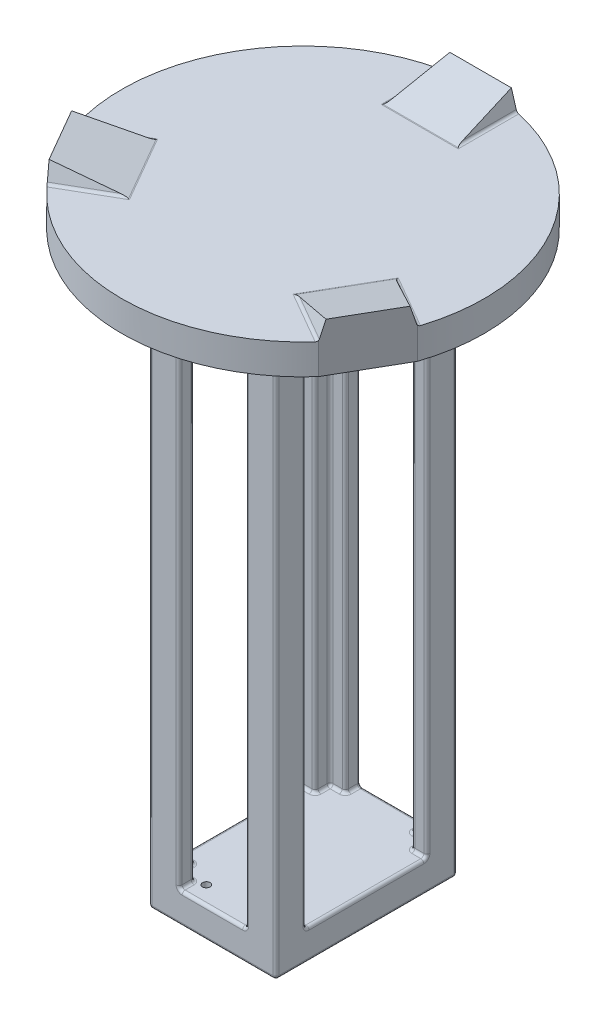
SolidWorks part; units mm, degrees
ref_plane "Plan de face" through (0, 0, 0) normal (0, 0, 1) x (1, 0, 0)
ref_plane "Plan de dessus" through (0, 0, 0) normal (0, 1, 0) x (1, 0, 0)
ref_plane "Plan de droite" through (0, 0, 0) normal (1, 0, 0) x (0, 0, -1)
sketch "Esquisse1" plane through (0, 0, 0) normal (0, 1, 0) x (1, 0, 0)
  line L29 (-12, 58.7878) -> (12, 58.7878)
  line L30 (56.9117, -19.0016) -> (44.9117, -39.7862)
  line L31 (-44.9117, -39.7862) -> (-56.9117, -19.0016)
  arc A4 (-12, 58.7878) -> (-56.9117, -19.0016) centre (0, 0) ccw
  arc A5 (-44.9117, -39.7862) -> (44.9117, -39.7862) centre (0, 0) ccw
  arc A6 (12, 58.7878) -> (56.9117, -19.0016) centre (0, 0) cw
  point P17 (0, 0)
  dimension "D1" = 24
  dimension "D4" = 24
  dimension "D5" = 60
  dimension "D6" = 60
  dimension "D3" = 60
  dimension "D2" = 24
  dimension "D7" = 56.9117
  dimension "D8" = 56.9117
extrude "Boss.-Extru.1" add sketch "Esquisse1" along normal mid plane 10
sketch "Esquisse3" plane through (0, -5, 0) normal (0, -1, 0) x (1, 0, 0)
  line L68 (21, 30) -> (11, 30)
  line L69 (21, -30) -> (-21, -30) construction
  line L70 (21, -30) -> (21, 30) construction
  line L71 (21, 30) -> (-21, 30) construction
  line L72 (-21, -30) -> (-21, 30) construction
  line L73 (21, -20) -> (16, -20)
  line L74 (16, -20) -> (16, -25)
  line L75 (11, 30) -> (11, 25)
  line L76 (11, 25) -> (16, 25)
  line L77 (16, 25) -> (16, 20)
  line L78 (16, 20) -> (21, 20)
  line L79 (21, 20) -> (21, 30)
  line L80 (21, -30) -> (21, -20)
  line L81 (16, -25) -> (11, -25)
  line L82 (11, -25) -> (11, -30)
  line L83 (-21, -30) -> (-21, -20)
  line L84 (-21, -20) -> (-16, -20)
  line L85 (-16, -20) -> (-16, -25)
  line L86 (-16, -25) -> (-11, -25)
  line L87 (-11, -25) -> (-11, -30)
  line L88 (-11, -30) -> (-21, -30)
  line L89 (-21, 30) -> (-21, 20)
  line L90 (-21, 20) -> (-16, 20)
  line L91 (-16, 20) -> (-16, 25)
  line L92 (-16, 25) -> (-11, 25)
  line L93 (-11, 25) -> (-11, 30)
  line L94 (-11, 30) -> (-21, 30)
  line L95 (11, -30) -> (21, -30)
  point P0 (0, 0)
  dimension "D1" = 42
  dimension "D2" = 60
  dimension "D3" = 10
  dimension "D4" = 10
  dimension "D5" = 5
  dimension "D6" = 5
  dimension "D7" = 25
  dimension "D8" = 5
  dimension "D9" = 5
  dimension "D10" = 5
  dimension "D11" = 10
  dimension "D12" = 5
  dimension "D13" = 5
  dimension "D14" = 5
  dimension "D15" = 10
  dimension "D16" = 16
extrude "Boss.-Extru.2" add sketch "Esquisse3" along normal blind 180
sketch "Esquisse7" plane through (0, -185, 0) normal (0, -1, 0) x (1, 0, 0)
  line L12 (21, -30) -> (-21, 30) construction
  line L13 (21, 30) -> (-21, -30) construction
  line L15 (21, -30) -> (-21, -30)
  line L16 (21, -30) -> (21, 30)
  line L17 (21, 30) -> (-21, 30)
  line L18 (-21, -30) -> (-21, 30)
  line L19 (21, -30) -> (-21, 30) construction
  line L20 (21, 30) -> (-21, -30) construction
  point P0 (0, 0)
  point P9 (0, 0)
  dimension "D1" = 42
  dimension "D2" = 60
extrude "Boss.-Extru.3" add sketch "Esquisse7" along normal blind 10
fillet "Congé3" radius 1 72 edges at (-18.5, -185, 20) (-18.5, -5, 20) (-16, -95, 20) (-16, -185, 22.5) (-16, -5, 22.5) (-16, -95, 25) (-13.5, -185, 25) (-13.5, -5, 25) (-11, -95, 25) (-11, -185, 27.5) (-11, -5, 27.5) (18.5, -185, -20) (18.5, -5, -20) (16, -95, -20) (16, -185, -22.5) (16, -5, -22.5) (16, -95, -25) (13.5, -185, -25) (13.5, -5, -25) (11, -95, -25) (11, -185, -27.5) (11, -5, -27.5) (11, -185, 27.5) (11, -5, 27.5) (11, -95, 25) (13.5, -185, 25) (13.5, -5, 25) (16, -95, 25) (16, -185, 22.5) (16, -5, 22.5) (16, -95, 20) (18.5, -185, 20) (18.5, -5, 20) (-11, -185, -27.5) (-11, -5, -27.5) (-11, -95, -25) (-13.5, -185, -25) (-13.5, -5, -25) (-16, -95, -25) (-16, -185, -22.5) (-16, -5, -22.5) (-16, -95, -20) (-18.5, -185, -20) (-18.5, -5, -20) (21, -5, 25) (21, -95, 20) (21, -95, -20) (21, -5, -25) (11, -95, -30) (-11, -95, -30) (-16, -5, -30) (21, -100, -30) (16, -5, -30) (-21, -100, -30) (-21, -5, -25) (-21, -95, -20) (-21, -95, 20) (-21, -5, 25) (-11, -95, 30) (11, -95, 30) (16, -5, 30) (21, -100, 30) (-21, -100, 30) (-16, -5, 30) (21, -195, 0) (21, -185, 0) (0, -185, -30) (0, -195, -30) (-21, -195, 0) (-21, -185, 0) (0, -185, 30) (0, -195, 30)
sketch "Esquisse8" plane through (0, -195, 0) normal (0, -1, 0) x (1, 0, 0)
  line L1 (0, -55) -> (0, 55) construction
  line L3 (20, 29) -> (-20, 29) construction
  circle A0 centre (8, 24) radius 1.25
  circle A1 centre (-8, 24) radius 1.25
  dimension "D2" = 2.5
  dimension "D1" = 8
  dimension "D3" = 5
extrude "Enlèv. mat.-Extru.4" cut sketch "Esquisse8" against normal up to next
sketch "Esquisse13" plane through (0, 0, -58.7878) normal (0, 0, -1) x (-1, 0, 0)
  line L2 (-10.185, 11.1348) -> (10.185, 11.1348)
  line L5 (-10.185, 11.1348) -> (-12, 5)
  line L6 (10.185, 11.1348) -> (12, 5)
  line L7 (-12, 5) -> (12, 5)
  point P4 (0, 11.1348)
  dimension "D1" = 20.37
  dimension "D2" = 6.1348
extrude "Boss.-Extru.4" add sketch "Esquisse13" against normal blind 20
sketch "Esquisse15" plane through (0, 0, 0) normal (1, 0, 0) x (0, 0, -1)
  line L0 (38.7878, 5) -> (58.7878, 11.1348)
  line L1 (58.7878, 11.1348) -> (38.7878, 11.1348)
  line L2 (38.7878, 11.1348) -> (38.7878, 5)
extrude "Enlèv. mat.-Extru.5" cut sketch "Esquisse15" against normal through all both and the other way through all
fillet "Congé9" radius 1 3 edges at (12, 5, -48.7878) (0, 5, -38.7878) (-12, 5, -48.7878)
pattern_circular "Répétition circulaire2" count 3 over 360 about axis through (0, 5, 0) along (0, 1, 0) of "Boss.-Extru.4", "Enlèv. mat.-Extru.5", "Congé9"
